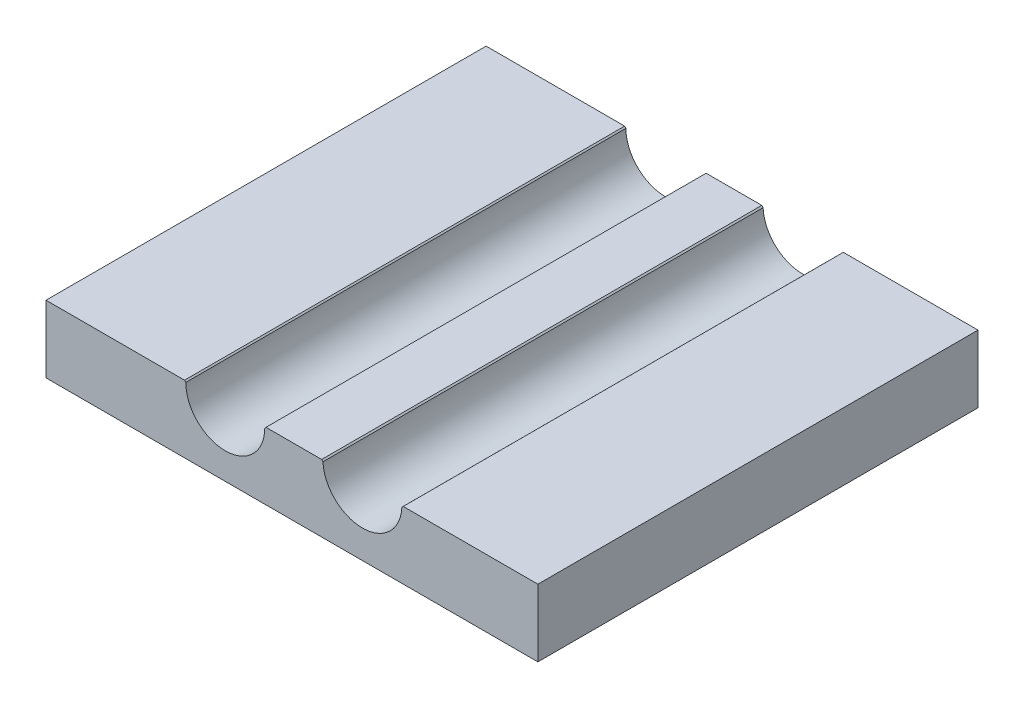
SolidWorks part; units mm, degrees
material "Copper"
ref_plane "Front Plane" through (0, 0, 0) normal (0, 0, 1) x (1, 0, 0)
ref_plane "Top Plane" through (0, 0, 0) normal (0, 1, 0) x (1, 0, 0)
ref_plane "Right Plane" through (0, 0, 0) normal (1, 0, 0) x (0, 0, -1)
sketch "Sketch1" plane through (0, 0, 0) normal (0, 1, 0) x (1, 0, 0)
  line L0 (-19, 17) -> (19, -17) construction
  line L1 (-19, 17) -> (19, 17)
  line L2 (-19, 17) -> (-19, -17)
  line L3 (-19, -17) -> (19, -17)
  line L4 (19, 17) -> (19, -17)
  dimension "D1" = 38
  dimension "D2" = 34
extrude "Boss-Extrude1" add sketch "Sketch1" along normal blind 2
sketch "Sketch2" plane through (0, 0, 17) normal (0, 0, 1) x (1, 0, 0)
  line L0 (-2.1012, 5.1925) -> (2.3945, 5.1925)
  line L1 (-8.198, 5.1985) -> (-19, 5.1985)
  line L3 (-19, 5.1985) -> (-19, 1.6624)
  line L4 (-19, 1.6624) -> (19, 1.6624)
  line L5 (19, 1.6624) -> (19, 5.1995)
  line L6 (19, 5.1995) -> (8.4942, 5.1995)
  line L7 (-19, 2) -> (-19, 0) construction
  line L8 (19, 2) -> (19, 0) construction
  arc A0 (-8.198, 5.1985) -> (-2.1012, 5.1925) centre (-5.1497, 5.0965) ccw
  arc A1 (2.3945, 5.1925) -> (8.4942, 5.1995) centre (5.4443, 5.2278) ccw
  dimension "D1" = 6.1
  dimension "D2" = 6.1
extrude "Boss-Extrude2" add sketch "Sketch2" against normal through all
chamfer "Chamfer1" distance 0.1 angle 45 4 edges at (2.3945, 5.1925, 0) (-2.1012, 5.1925, 0) (-8.198, 5.1985, 0) (8.4942, 5.1995, 0) first distance on face at (0.1467, 5.1925, 0) first distance on face at (-5.1511, 3.621, 0) first distance on face at (-13.599, 5.1985, 0) first distance on face at (5.4461, 3.6869, 0)
